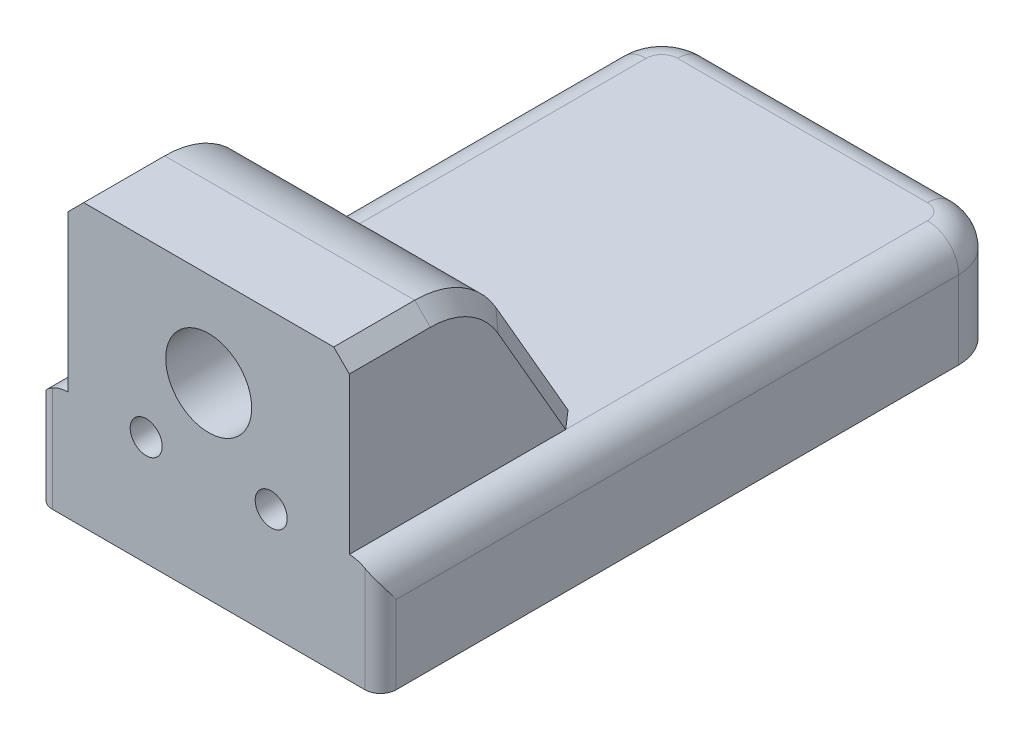
SolidWorks part; units mm, degrees
ref_plane "前视基准面" through (0, 0, 0) normal (0, 0, 1) x (1, 0, 0)
ref_plane "上视基准面" through (0, 0, 0) normal (0, 1, 0) x (1, 0, 0)
ref_plane "右视基准面" through (0, 0, 0) normal (1, 0, 0) x (0, 0, -1)
other "Configuration Table"
ref_plane "基准面2" through (0, 0, 0) normal (0, -1, 0) x (1, 0, 0)
sketch "草图2" plane through (0, 0, 0) normal (0, -1, 0) x (1, 0, 0)
  line L0 (0, 0) -> (0, -40)
  line L1 (0, -40) -> (22, -40)
  line L2 (22, -40) -> (22, 0)
  line L3 (22, 0) -> (0, 0)
  dimension "D1" = 22
  dimension "D2" = 40
extrude "凸台-拉伸1" add sketch "草图2" against normal blind 7
sketch "草图3" plane through (0, 7, 0) normal (0, 1, 0) x (-1, 0, 0)
  line L0 (-20, 0) -> (-2, 0)
  line L1 (-2, 0) -> (-2, -15)
  line L2 (-2, -15) -> (-20, -15)
  line L3 (-20, -15) -> (-20, 0)
  line L4 (-22, -40) -> (-22, 0) construction
  line L5 (-22, 0) -> (0, 0) construction
  dimension "D1" = 2
  dimension "D2" = 20
  dimension "D3" = 15
extrude "凸台-拉伸2" add sketch "草图3" along normal blind 11
draft "拔模1" type of draft neutral plane draft angle 30 faces to draft 1 face at (11, 12.5, -15) neutral plane through (0, 7, 0) neutral plane normal (0, 1, 0) parameters "D1"=30
hole_wizard "孔1" positions "草图5" profile "草图4" legacy
sketch "草图5" plane through (0, 0, 0) normal (0, 0, 1) x (1, 0, 0)
  point P0 (7, 7)
sketch "草图4" plane through (7, 7, 0) normal (1, 0, 0) x (0, -1, 0)
  line L0 (0, 0) -> (0, 5)
  line L1 (0, 5) -> (1.025, 5)
  line L2 (1.025, 5) -> (1.025, 0)
  line L3 (1.025, 0) -> (0, 0)
  line L4 (0, 110) -> (0, -10) construction
  dimension "直径" = 2.05
  dimension "深度" = 5
hole_wizard "孔2" positions "草图7" profile "草图6" legacy
sketch "草图7" plane through (0, 0, 0) normal (0, 0, 1) x (1, 0, 0)
  point P0 (15, 7)
sketch "草图6" plane through (15, 7, 0) normal (1, 0, 0) x (0, -1, 0)
  line L0 (0, 0) -> (0, 5)
  line L1 (0, 5) -> (1.025, 5)
  line L2 (1.025, 5) -> (1.025, 0)
  line L3 (1.025, 0) -> (0, 0)
  line L4 (0, 110) -> (0, -10) construction
  dimension "直径" = 2.05
  dimension "深度" = 5
ref_plane "基准面3" through (0, 0, -14.7113) normal (0, 0, -1) x (-1, 0, 0)
hole_wizard "孔3" positions "草图9" profile "草图8" legacy
sketch "草图9" plane through (0, 0, -14.7113) normal (0, 0, -1) x (-1, 0, 0)
  point P0 (-11, 12)
sketch "草图8" plane through (11, 12, -14.7113) normal (1, 0, 0) x (0, 1, 0)
  line L0 (0, 0) -> (0, 14.7113)
  line L1 (0, 14.7113) -> (2.75, 14.7113)
  line L2 (2.75, 14.7113) -> (2.75, 10.7113)
  line L3 (2.75, 10.7113) -> (4.5, 10.7113)
  line L4 (4.5, 10.7113) -> (4.5, 0)
  line L5 (4.5, 0) -> (0, 0)
  line L6 (0, 110) -> (0, -10) construction
  dimension "直径" = 5.5
  dimension "深度" = 14.7113
  dimension "柱坑直径" = 9
  dimension "柱坑深度" = 10.7113
fillet "圆角1" radius 3 2 edges at (22, 3.5, -40) (0, 3.5, -40) tangent propagation no
fillet "圆角2" radius 2 5 edges at (0, 7, -18.5) (0.8787, 7, -39.1213) (11, 7, -40) (21.1213, 7, -39.1213) (22, 7, -18.5) tangent propagation no
fillet "圆角3" radius 6 1 edges at (11, 18, -8.6491) tangent propagation no
chamfer "倒角1" distance 1 angle 45 6 edges at (20, 18, -2.5925) (20, 11, -12.6906) (20, 17.1962, -8.185) (2, 18, -2.5925) (2, 17.1962, -8.185) (2, 11, -12.6906)
fillet "圆角4" radius 1 2 edges at (0, 2.5, 0) (22, 2.5, 0) tangent propagation no
